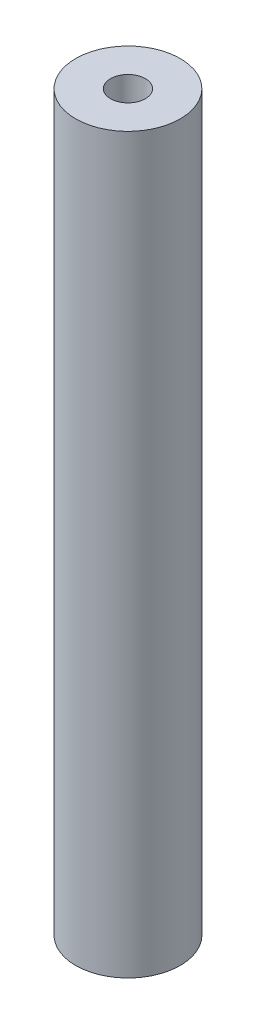
SolidWorks part; units mm, degrees
ref_plane "Front Plane" through (0, 0, 0) normal (0, 0, 1) x (1, 0, 0)
ref_plane "Top Plane" through (0, 0, 0) normal (0, 1, 0) x (1, 0, 0)
ref_plane "Right Plane" through (0, 0, 0) normal (1, 0, 0) x (0, 0, -1)
sketch "Sketch1" plane through (0, 0, 0) normal (0, 1, 0) x (1, 0, 0)
  circle A0 centre (0, 0) radius 47.625
  circle A1 centre (0, 0) radius 15.875
  dimension "D1" = 95.25
  dimension "D2" = 31.75
extrude "Boss-Extrude1" add sketch "Sketch1" along normal mid plane 668.02
